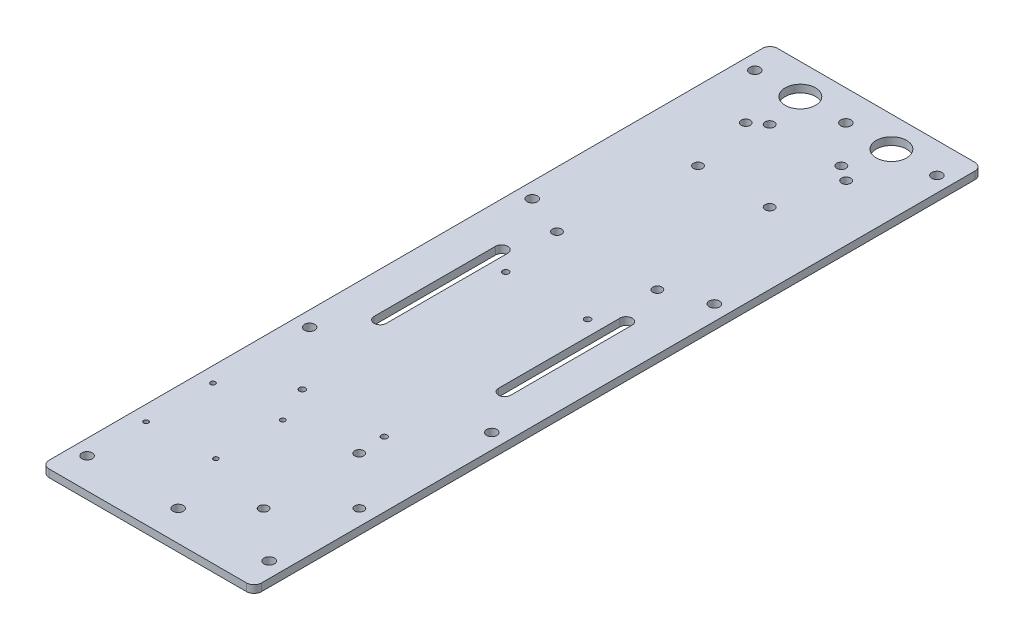
SolidWorks part; units mm, degrees
ref_plane "Front Plane" through (0, 0, 0) normal (0, 0, 1) x (1, 0, 0)
ref_plane "Top Plane" through (0, 0, 0) normal (0, 1, 0) x (1, 0, 0)
ref_plane "Right Plane" through (0, 0, 0) normal (1, 0, 0) x (0, 0, -1)
sketch "Sketch2" plane through (0, 0, 0) normal (0, 1, 0) x (1, 0, 0)
  line L0 (-44.45, 0) -> (44.45, 0) construction
  line L1 (-41.275, 152.4) -> (41.275, 152.4)
  line L2 (-44.45, 149.225) -> (-44.45, -149.225)
  line L3 (-41.275, -152.4) -> (41.275, -152.4)
  line L4 (44.45, 149.225) -> (44.45, -149.225)
  line L5 (0, 152.4) -> (0, -152.4) construction
  arc A0 (-44.45, -149.225) -> (-41.275, -152.4) centre (-41.275, -149.225) ccw
  arc A1 (41.275, -152.4) -> (44.45, -149.225) centre (41.275, -149.225) ccw
  arc A2 (41.275, 152.4) -> (44.45, 149.225) centre (41.275, 149.225) cw
  arc A3 (-41.275, 152.4) -> (-44.45, 149.225) centre (-41.275, 149.225) ccw
  point P8 (0, 0)
  point P13 (-44.45, -152.4)
  point P16 (44.45, -152.4)
  point P21 (-44.45, 152.4)
  dimension "D3" = 3.175
  dimension "D1" = 304.8
  dimension "D2" = 88.9
extrude "Plate Thickness" add sketch "Sketch2" along normal blind 3.175 contours L2 A0 L3 A1 L4 A2 L1 A3
sketch "Sketch3" plane through (0, 3.175, 0) normal (0, 1, 0) x (1, 0, 0)
  line L0 (-44.45, 149.225) -> (-44.45, -149.225) construction
  line L1 (-41.275, 152.4) -> (41.275, 152.4) construction
  line L4 (0, 152.4) -> (0, -152.4) construction
  line L5 (-41.275, -152.4) -> (41.275, -152.4) construction
  line L6 (-41.275, -152.4) -> (41.275, -152.4) construction
  circle A0 centre (-38.1, 139.7) radius 2.159
  circle A1 centre (-38.1, 46.5667) radius 2.159
  circle A2 centre (-38.1, -46.5667) radius 2.159
  circle A3 centre (-38.1, -139.7) radius 2.159
  circle A4 centre (38.1, -139.7) radius 2.159
  circle A5 centre (38.1, -46.5667) radius 2.159
  circle A6 centre (38.1, 46.5667) radius 2.159
  circle A7 centre (38.1, 139.7) radius 2.159
  circle A8 centre (0, 139.7) radius 2.159
  circle A9 centre (0, -139.7) radius 2.159
  dimension "D1" = 4.318
  dimension "D4" = 4.318
  dimension "D2" = 6.35
  dimension "D3" = 12.7
  dimension "D5" = 12.7
  dimension "D6" = 12.7
  dimension "D7" = 93.1333
  dimension "D8" = 93.1333
extrude "Mounting holes" cut sketch "Sketch3" against normal through all
sketch "Sketch4" plane through (0, 3.175, 0) normal (0, 1, 0) x (1, 0, 0)
  line L0 (-21.0058, 39.8143) -> (21.0058, 39.8143) construction
  line L1 (0, 0) -> (0, 139.7) construction
  circle A0 centre (-21.0058, 118.8083) radius 1.905
  circle A1 centre (-21.0058, 39.8143) radius 1.905
  circle A2 centre (21.0058, 39.8143) radius 1.905
  circle A3 centre (21.0058, 118.8083) radius 1.905
  point P13 (0, 39.8143)
  point P17 (0, 69.85)
  point P18 (0, 69.85)
  dimension "D1" = 3.81
  dimension "D2" = 78.994
  dimension "D3" = 42.0116
extrude "Jetson Holes (w/o mount)" cut sketch "Sketch4" against normal through all
sketch "Sketch5" plane through (0, 3.175, 0) normal (0, 1, 0) x (1, 0, 0)
  line L0 (-41.275, 152.4) -> (41.275, 152.4) construction
  line L1 (44.45, 149.225) -> (44.45, -149.225) construction
  circle A1 centre (-15.3784, 123.19) radius 1.905
  circle A3 centre (14.619, 123.19) radius 1.905
  circle A4 centre (14.619, 93.1926) radius 1.905
  circle A5 centre (-15.3784, 93.1926) radius 1.905
  dimension "D1" = 3.81
  dimension "D2" = 29.9974
  dimension "D4" = 29.21
  dimension "D5" = 29.831
  dimension "D3" = 29.9974
extrude "PDB holes" cut sketch "Sketch5" against normal through all
sketch "Sketch6" plane through (0, 3.175, 0) normal (0, 1, 0) x (1, 0, 0)
  circle A6 centre (37.9175, -101.7966) radius 1.905
  circle A7 centre (17.9175, -81.8626) radius 1.905
  circle A8 centre (17.9175, -121.8626) radius 1.905
  dimension "D5" = 3.81
  dimension "D6" = 40
  dimension "D7" = 20
  dimension "D8" = 20.066
sketch "Sketch7" plane through (0, 3.175, 0) normal (0, 1, 0) x (1, 0, 0)
  line L0 (0, 152.4) -> (0, -152.4) construction
  line L1 (-41.275, 152.4) -> (41.275, 152.4) construction
  line L2 (-41.275, -152.4) -> (41.275, -152.4) construction
  line L3 (17.145, 14.4893) -> (-17.145, 14.4893) construction
  circle A0 centre (-17.145, 14.4893) radius 1.27
  circle A1 centre (-17.145, -70.6007) radius 1.27
  circle A2 centre (17.145, -70.6007) radius 1.27
  circle A3 centre (17.145, 14.4893) radius 1.27
  point P14 (0, 14.4893)
  dimension "D1" = 2.54
  dimension "D2" = 85.09
  dimension "D3" = 34.29
extrude "PixHawk Holes" cut sketch "Sketch7" against normal through all
sketch "Sketch8" plane through (0, 3.175, 0) normal (0, 1, 0) x (1, 0, 0)
  line L0 (0, 152.4) -> (0, -115.5095) construction
  line L1 (-41.275, 152.4) -> (41.275, 152.4) construction
  line L2 (-26.035, 21.6897) -> (-26.035, -29.1103) construction
  line L3 (-23.495, 21.6897) -> (-23.495, -29.1103)
  line L4 (-28.575, 21.6897) -> (-28.575, -29.1103)
  line L5 (26.035, 21.6897) -> (26.035, -29.1103) construction
  line L6 (23.495, 21.6897) -> (23.495, -29.1103)
  line L7 (28.575, 21.6897) -> (28.575, -29.1103)
  arc A0 (-23.495, 21.6897) -> (-28.575, 21.6897) centre (-26.035, 21.6897) ccw
  arc A1 (-28.575, -29.1103) -> (-23.495, -29.1103) centre (-26.035, -29.1103) ccw
  arc A2 (23.495, 21.6897) -> (28.575, 21.6897) centre (26.035, 21.6897) cw
  arc A3 (28.575, -29.1103) -> (23.495, -29.1103) centre (26.035, -29.1103) cw
  point P7 (-26.035, -3.7103)
  point P14 (26.035, -3.7103)
  dimension "D1" = 50.8
  dimension "D2" = 5.08
  dimension "D3" = 26.035
extrude "Battery Holes" cut sketch "Sketch8" against normal through all
sketch "Sketch9" plane through (0, 3.175, 0) normal (0, 1, 0) x (1, 0, 0)
  line L0 (44.45, 149.225) -> (44.45, -149.225) construction
  line L1 (-41.275, -152.4) -> (41.275, -152.4) construction
  circle A0 centre (6.8334, -85.3) radius 2
  circle A1 centre (34.3334, -85.3) radius 2
  circle A2 centre (34.3334, -114.3) radius 2
  circle A3 centre (6.8334, -114.3) radius 2
  dimension "D1" = 4
  dimension "D3" = 10.1166
  dimension "D5" = 38.1
  dimension "D2" = 27.5
  dimension "D4" = 29
sketch "Sketch10" plane through (0, 3.175, 0) normal (0, 1, 0) x (1, 0, 0)
  line L0 (-44.45, 149.225) -> (-44.45, -149.225) construction
  circle A0 centre (-38.1255, -87.0086) radius 1
  circle A1 centre (-38.1, -115.0086) radius 1
  circle A2 centre (-10.1266, -85.7891) radius 1
  circle A3 centre (-10.1266, -113.7891) radius 1
  dimension "D1" = 2
  dimension "D2" = 28
  dimension "D3" = 28
  dimension "D4" = 28
  dimension "D5" = 6.35
extrude "Ventral Camera holes" cut sketch "Sketch10" against normal up to next
sketch "Sketch12" plane through (0, 3.175, 0) normal (0, 1, 0) x (1, 0, 0)
  line L0 (-41.275, 152.4) -> (41.275, 152.4) construction
  circle A0 centre (-19.05, 139.7) radius 6.35
  circle A1 centre (19.05, 139.7) radius 6.35
  circle A2 centre (-38.1, 139.7) radius 2.159 construction
  dimension "D1" = 19.05
  dimension "D3" = 12.7
  dimension "D2" = 38.1
  dimension "D4" = 12.7
extrude "Wifi antenna holes" cut sketch "Sketch12" against normal through all
extrude "Cut-Extrude1" cut sketch "Sketch6" against normal through all
